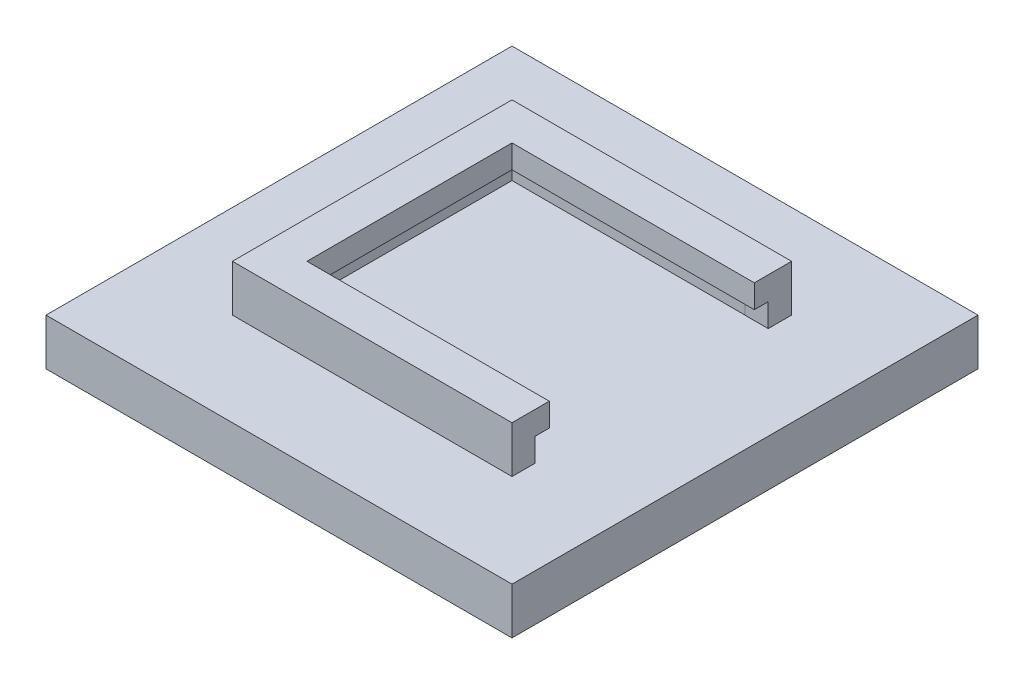
SolidWorks part; units mm, degrees
ref_plane "Front Plane" through (0, 0, 0) normal (0, 0, 1) x (1, 0, 0)
ref_plane "Top Plane" through (0, 0, 0) normal (0, 1, 0) x (1, 0, 0)
ref_plane "Right Plane" through (0, 0, 0) normal (1, 0, 0) x (0, 0, -1)
sketch "Sketch1" plane through (0, 0, 0) normal (0, 1, 0) x (1, 0, 0)
  line L1 (50, -50) -> (-50, -50)
  line L2 (50, -50) -> (50, 50)
  line L3 (50, 50) -> (-50, 50)
  line L4 (-50, -50) -> (-50, 50)
  line L5 (50, -50) -> (-50, 50) construction
  line L6 (50, 50) -> (-50, -50) construction
  point P0 (0, 0)
  dimension "D1" = 100
  dimension "D2" = 100
extrude "Boss-Extrude1" add sketch "Sketch1" along normal blind 10
sketch "Sketch2" plane through (0, 0, 0) normal (0, 1, 0) x (1, 0, 0)
  line L1 (-25, 25) -> (25, 25)
  line L2 (-25, 25) -> (-25, -25)
  line L3 (-25, -25) -> (25, -25)
  line L4 (25, 25) -> (25, -25)
  line L5 (-25, 25) -> (25, -25) construction
  line L6 (-25, -25) -> (25, 25) construction
  point P0 (0, 0)
  dimension "D1" = 50
  dimension "D2" = 50
extrude "Extrude-Thin1" add sketch "Sketch2" along normal blind 15 thin thin type one direction wall 5
sketch "Sketch3" plane through (0, 15, 0) normal (0, 1, 0) x (1, 0, 0)
  line L0 (30, -30) -> (30, 30) construction
  line L1 (25, -25.0256) -> (30, -25.0256)
  line L2 (25, -25.0256) -> (25, 24.9744)
  line L3 (25, 24.9744) -> (30, 24.9744)
  line L4 (30, -25.0256) -> (30, 24.9744)
  line L5 (25, -25.0256) -> (30, 24.9744) construction
  line L6 (25, 24.9744) -> (30, -25.0256) construction
  point P1 (27.5, -0.0256)
  point P8 (0, 0)
  point P9 (0, 0)
  point P10 (27.5578, 0.1066)
  dimension "D1" = 50
  dimension "D2" = 5
extrude "Cut-Extrude1" cut sketch "Sketch3" against normal blind 5
sketch "Sketch4" plane through (0, 15, 0) normal (0, 1, 0) x (1, 0, 0)
  line L1 (30, 30) -> (-30, 30)
  line L2 (30, 30) -> (30, -30)
  line L3 (30, -30) -> (-30, -30)
  line L4 (-30, 30) -> (-30, -30)
  line L5 (30, 30) -> (-30, -30) construction
  line L6 (30, -30) -> (-30, 30) construction
  point P0 (0, 0)
extrude "Boss-Extrude2" add sketch "Sketch4" along normal blind 5
sketch "Sketch5" plane through (0, 20, 0) normal (0, 1, 0) x (1, 0, 0)
  line L0 (30, -30) -> (30, 30) construction
  line L1 (-22, -22) -> (30, -22)
  line L2 (-22, -22) -> (-22, 22)
  line L3 (-22, 22) -> (30, 22)
  line L4 (30, -22) -> (30, 22)
  line L5 (-22, -22) -> (30, 22) construction
  line L6 (-22, 22) -> (30, -22) construction
  line L7 (-30, -30) -> (30, -30) construction
  point P0 (4, 0)
  dimension "D1" = 44
  dimension "D2" = 52
  dimension "D3" = 8
extrude "Cut-Extrude2" cut sketch "Sketch5" against normal blind 5
